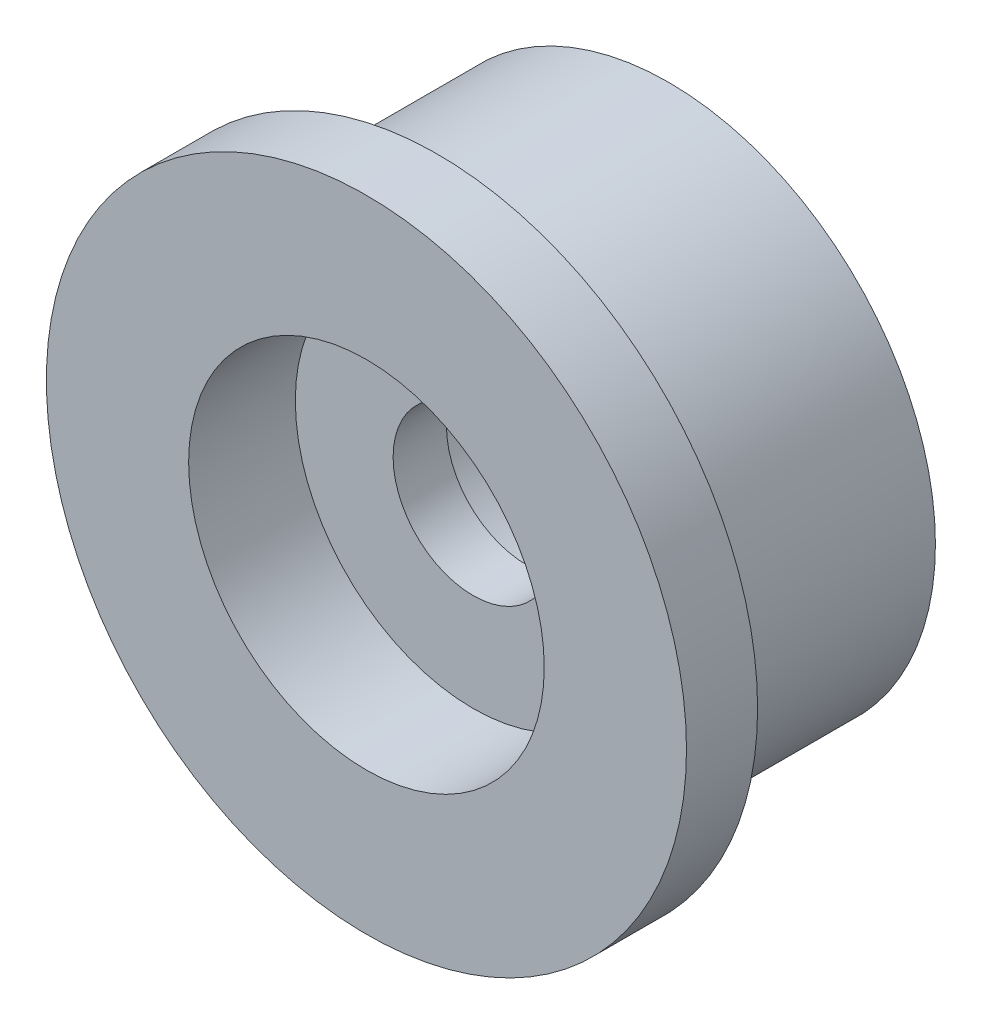
SolidWorks part; units mm, degrees
ref_plane "前视基准面" through (0, 0, 0) normal (0, 0, 1) x (1, 0, 0)
ref_plane "上视基准面" through (0, 0, 0) normal (0, 1, 0) x (1, 0, 0)
ref_plane "右视基准面" through (0, 0, 0) normal (1, 0, 0) x (0, 0, -1)
sketch "草图1" plane through (0, 0, 0) normal (0, 0, 1) x (1, 0, 0)
  circle A0 centre (0, 0) radius 9
extrude "凸台-拉伸1" add sketch "草图1" along normal blind 2
sketch "草图2" plane through (0, 0, 0) normal (0, 0, 1) x (1, 0, 0)
  circle A0 centre (0, 0) radius 7.5
extrude "凸台-拉伸2" add sketch "草图2" against normal blind 6.5
ref_plane "基准面1" through (0, 0, -6.5) normal (0, 0, -1) x (-1, 0, 0)
sketch "草图5" plane through (0, 0, -6.5) normal (0, 0, -1) x (-1, 0, 0)
  circle A0 centre (0, 0) radius 3.9
extrude "切除-拉伸3" cut sketch "草图5" against normal blind 4
sketch "草图6" plane through (0, 0, -6.5) normal (0, 0, -1) x (-1, 0, 0)
  circle A0 centre (0, 0) radius 2.25
extrude "切除-拉伸4" cut sketch "草图6" against normal through all
sketch "草图7" plane through (0, 0, 0) normal (0, 0, 1) x (1, 0, 0)
  circle A0 centre (0, 0) radius 5
extrude "切除-拉伸5" cut sketch "草图7" along normal blind 2 and the other way blind 1
